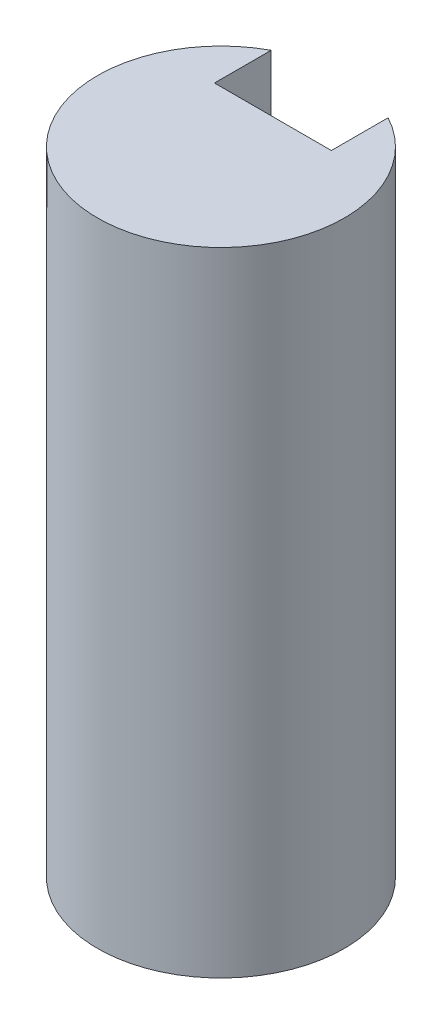
SolidWorks part; units mm, degrees
note: The reader was unsure of these and kept them because the rebuilt part matched: shared geometry of "Sketch1<3>".
ref_plane "Front Plane" through (0, 0, 0) normal (0, 0, 1) x (1, 0, 0)
ref_plane "Top Plane" through (0, 0, 0) normal (0, 1, 0) x (1, 0, 0)
ref_plane "Right Plane" through (0, 0, 0) normal (1, 0, 0) x (0, 0, -1)
sketch "Sketch1" plane through (0, 0, 0) normal (0, 1, 0) x (1, 0, 0)
  line L1 (4.5, 4) -> (-4.5, 4)
  line L2 (4.5, 4) -> (4.5, 15)
  line L3 (4.5, 15) -> (-4.5, 15)
  line L4 (-4.5, 4) -> (-4.5, 15)
  line L5 (4.5, 4) -> (-4.5, 15) construction
  line L6 (4.5, 15) -> (-4.5, 4) construction
  circle A0 centre (0, 0) radius 9.5
  point P3 (0, 9.5)
  dimension "D3" = 19
  dimension "D1" = 9
  dimension "D2" = 11
extrude "Boss-Extrude1" add sketch "Sketch1" along normal blind 12.7 contours A0 L2 L3 L4 | L2 A0 L4 L1 | L4 A0 L2 L1
extrude "Boss-Extrude2" add sketch "Sketch1<3>" against normal blind 30 contours L4 A0 L2 L1 | L2 A0 L4 L1
sketch "Sketch1<3>" plane through (0, 0, 0) normal (0, 1, 0) x (1, 0, 0) same geometry as "Sketch1"
sketch "Sketch2" plane through (0, -30, 0) normal (0, -1, 0) x (1, 0, 0)
  line L0 (4.5, -4) -> (-4.5, -4) construction
  line L1 (-4.5, -4) -> (-4.5, -15) construction
  line L2 (4.5, -4) -> (4.5, -15) construction
  line L3 (4.5, -15) -> (-4.5, -15) construction
  line L4 (4.5, -4) -> (-4.5, -4)
  line L5 (-4.5, -4) -> (-4.5, -15)
  line L6 (4.5, -4) -> (4.5, -15)
  line L7 (4.5, -15) -> (-4.5, -15)
  circle A0 centre (0, 0) radius 9.5 construction
  circle A1 centre (0, 0) radius 9.5
  circle M1 centre (0, 0) radius 9.5
extrude "Boss-Extrude3" add sketch "Sketch2" along normal blind 6 contours L7 L6 L5 M1 | L6 L4 L5 M1 | L4 L6 L5 M1
equation "\"keyW_\"= \"keyW\" + \"clearance\""
equation "\"keyL_\"= \"keyL\" + \"clearance\""
equation "\"shaftDiam_\"= \"shaftDiam\" - \"clearance\""
equation "\"shaftDiam\" = 20mm"
equation "\"keyW\" = 8mm"
equation "\"keyL\" = 10mm"
equation "\"clearance\" = 1mm"
equation "\"handleShaftLen\" = 60mm"
equation "\"handleShaft\"= \"handleShaftLen\" / 2"
equation "\"turningHandle\"= \"handleShaftLen\""
equation "\"hole\"= \"shaftDiam\""
equation "\"fillet\"= \"shaftDiam\" / 5"
equation "\"D3@Sketch1\"=\"shaftDiam_\""
equation "\"D2@Sketch1\"=\"keyL_\""
equation "\"D1@Sketch1\"=\"keyW_\""
equation "\"D1@Boss-Extrude2\"=\"handleShaft\""
equation "\"D1@Boss-Extrude3\"=\"handleShaftLen\"/10"
